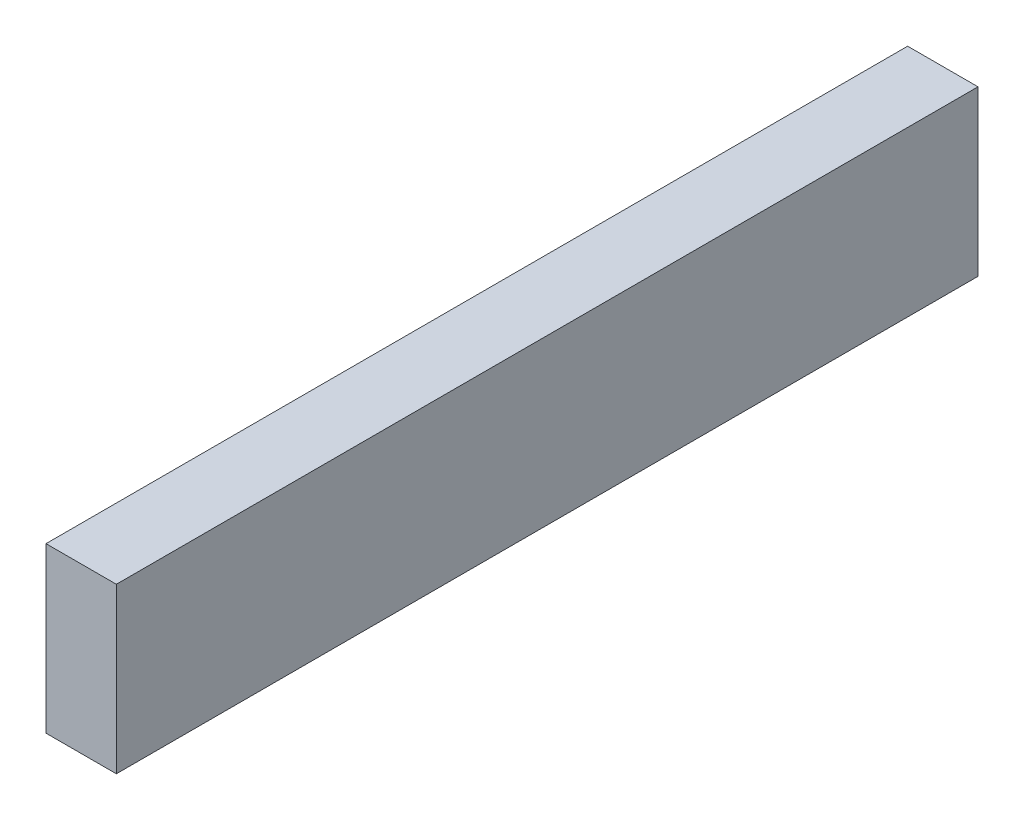
SolidWorks part; units mm, degrees
ref_plane "Front Plane" through (0, 0, 0) normal (0, 0, 1) x (1, 0, 0)
ref_plane "Top Plane" through (0, 0, 0) normal (0, 1, 0) x (1, 0, 0)
ref_plane "Right Plane" through (0, 0, 0) normal (1, 0, 0) x (0, 0, -1)
sketch "Sketch1" plane through (0, 0, 0) normal (0, 0, 1) x (1, 0, 0)
  line L1 (0, 0) -> (38.1, 0)
  line L2 (0, 0) -> (0, 88.9)
  line L3 (0, 88.9) -> (38.1, 88.9)
  line L4 (38.1, 0) -> (38.1, 88.9)
  dimension "D1" = 88.9
  dimension "D2" = 38.1
extrude "Boss-Extrude1" add sketch "Sketch1" along normal blind 466.598
